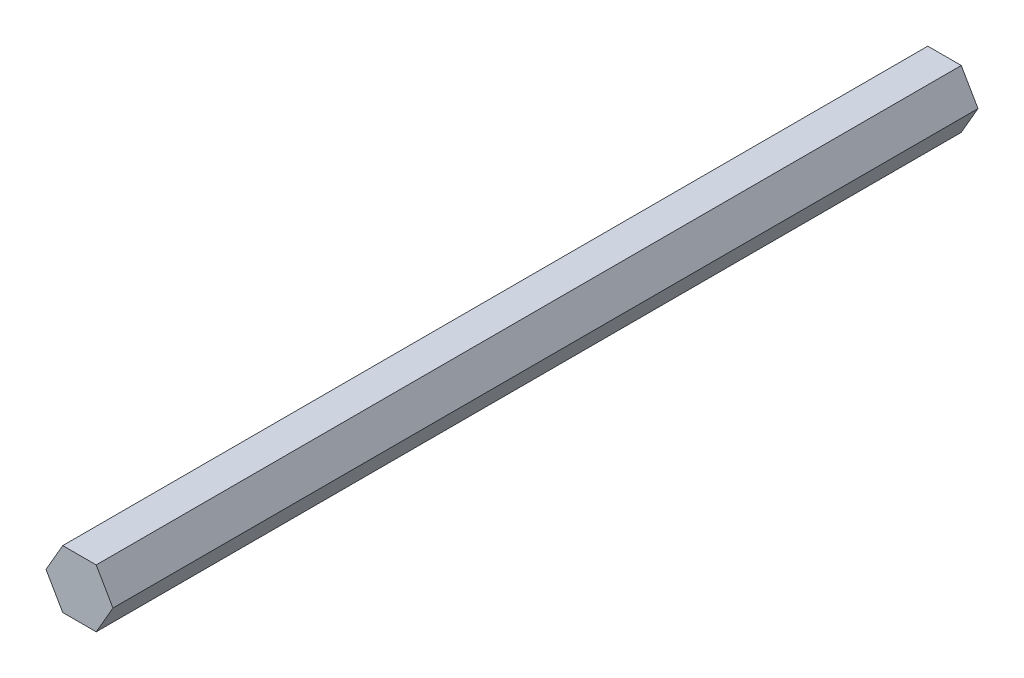
SolidWorks part; units mm, degrees
ref_plane "Alzado" through (0, 0, 0) normal (0, 0, 1) x (1, 0, 0)
ref_plane "Planta" through (0, 0, 0) normal (0, 1, 0) x (1, 0, 0)
ref_plane "Vista lateral" through (0, 0, 0) normal (1, 0, 0) x (0, 0, -1)
sketch "Croquis1" plane through (0, 0, 0) normal (0, 0, 1) x (1, 0, 0)
  line L1 (7.3323, 0) -> (3.6662, 6.35)
  line L2 (3.6662, 6.35) -> (-3.6662, 6.35)
  line L3 (-3.6662, 6.35) -> (-7.3323, 0)
  line L4 (-7.3323, 0) -> (-3.6662, -6.35)
  line L5 (-3.6662, -6.35) -> (3.6662, -6.35)
  line L6 (3.6662, -6.35) -> (7.3323, 0)
  circle A0 centre (0, 0) radius 6.35 construction
  dimension "D1" = 12.7
extrude "Saliente-Extruir1" add sketch "Croquis1" along normal blind 189.5
sketch "Croquis2" plane through (0, 0, 0) normal (0, 0, -1) x (-1, 0, 0)
  circle A0 centre (0, 0) radius 2.5
  dimension "D1" = 5
sketch "Croquis3" plane through (0, 0, 189.5) normal (0, 0, 1) x (1, 0, 0)
  circle A0 centre (0, 0) radius 2.5
  dimension "D1" = 5
